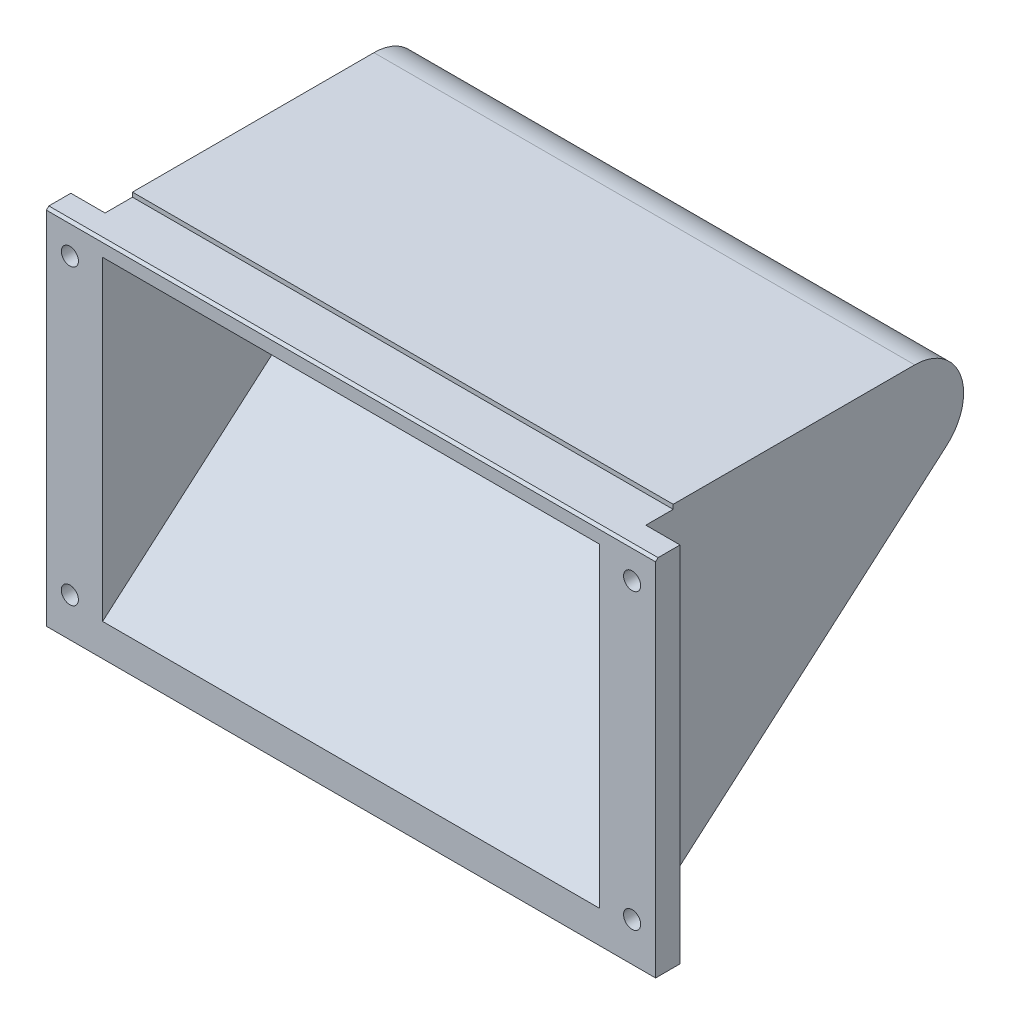
SolidWorks part; units mm, degrees
ref_plane "Front" through (0, 0, 0) normal (0, 0, 1) x (1, 0, 0)
ref_plane "Top" through (0, 0, 0) normal (0, 1, 0) x (1, 0, 0)
ref_plane "Right" through (0, 0, 0) normal (1, 0, 0) x (0, 0, -1)
sketch "Sketch1" plane through (0, 0, 0) normal (1, 0, 0) x (0, 0, -1)
  line L0 (0, 0) -> (60, 0)
  line L1 (63.2707, -8.7819) -> (0, -63.5)
  line L2 (0, 0) -> (0, 5)
  line L3 (0, 0) -> (0, -63.5) construction
  line L4 (0, 5) -> (60, 5)
  line L5 (66.5414, -12.5638) -> (0, -70.1105)
  line L6 (0, -70.1105) -> (0, -63.5)
  arc A0 (60, 0) -> (63.2707, -8.7819) centre (60, -5) cw
  arc A1 (60, 5) -> (66.5414, -12.5638) centre (60, -5) cw
  point P9 (73.4252, 0)
  dimension "D4" = 5
  dimension "D1" = 63.5
  dimension "D2" = 60
  dimension "D3" = 5
extrude "Boss-Extrude1" add sketch "Sketch1" along normal mid plane 101.6
sketch "Sketch3" plane through (50.8, 0, 0) normal (1, 0, 0) x (0, 0, -1)
  line L0 (0, 0) -> (0, -63.5)
  line L6 (0, 5) -> (0, 0)
  line L7 (0, 0) -> (60, 0)
  line L8 (63.2707, -8.7819) -> (0, -63.5)
  line L9 (0, -63.5) -> (0, -70.1105)
  line L10 (0, -70.1105) -> (66.5414, -12.5638)
  line L11 (60, 5) -> (0, 5)
  line L12 (0, 5) -> (0, 0)
  line L13 (0, 0) -> (60, 0)
  line L14 (63.2707, -8.7819) -> (0, -63.5)
  line L15 (0, -63.5) -> (0, -70.1105)
  line L16 (0, -70.1105) -> (66.5414, -12.5638)
  line L17 (60, 5) -> (0, 5)
  arc A2 (63.2707, -8.7819) -> (60, 0) centre (60, -5) ccw
  arc A3 (66.5414, -12.5638) -> (60, 5) centre (60, -5) ccw
  arc A4 (63.2707, -8.7819) -> (60, 0) centre (60, -5) ccw
  arc A5 (66.5414, -12.5638) -> (60, 5) centre (60, -5) ccw
  line M9 (0, 5) -> (0, 0)
  line M10 (0, 0) -> (60, 0)
  arc M11 (60, 0) -> (63.2707, -8.7819) centre (60, -5) cw
  line M12 (63.2707, -8.7819) -> (0, -63.5)
  line M13 (0, -63.5) -> (0, -70.1105)
  line M14 (0, -70.1105) -> (66.5414, -12.5638)
  arc M15 (66.5414, -12.5638) -> (60, 5) centre (60, -5) ccw
  line M16 (60, 5) -> (0, 5)
  dimension "D1" = 0
extrude "Boss-Extrude3" add sketch "Sketch3" along normal blind 4.5 contours M16 M9 M10 M11 M12 M13 M14 M15 | L0 M10 M12 M11 region at (50.8, -21.4686, -23.7908) region at (50.8, 2.5, -1.0267)
mirror "Mirror1" about plane through (0, 0, 0) normal (1, 0, 0) of "Boss-Extrude3"
sketch "Sketch4" plane through (0, 0, 0) normal (0, 0, 1) x (1, 0, 0)
  line L0 (-50.8, 5) -> (-50.8, -63.5)
  line L1 (55.3, 5) -> (-55.3, 5) construction
  line L2 (-50.8, -63.5) -> (50.8, -63.5)
  line L3 (50.8, -63.5) -> (50.8, 5)
  line L4 (50.8, 5) -> (62.3, 5)
  line L5 (62.3, 5) -> (62.3, -70.1105)
  line L6 (62.3, -70.1105) -> (-62.3, -70.1105)
  line L7 (-62.3, -70.1105) -> (-62.3, 5)
  line L8 (-62.3, 5) -> (-50.8, 5)
  line L9 (0, -63.5) -> (0, -70.1105) construction
  line L10 (55.3, 5) -> (55.3, -70.1105) construction
  line L11 (55.3, -70.1105) -> (-55.3, -70.1105) construction
  line M5 (-50.8, -63.5) -> (-50.8, 0)
  line M7 (50.8, 0) -> (50.8, -63.5)
  line M8 (50.8, -63.5) -> (-50.8, -63.5)
  line M9 (55.3, 5) -> (-55.3, 5)
  line M10 (-55.3, 5) -> (-55.3, -70.1105)
  line M11 (-55.3, -70.1105) -> (55.3, -70.1105)
  line M12 (55.3, -70.1105) -> (55.3, 5)
  dimension "D1" = 7
extrude "Boss-Extrude4" add sketch "Sketch4" against normal blind 5 contours L9 L2 L0 M5 M9 M10 M11 | L9 L8 L7 L6 M11 M10 | L9 L6 L5 L4 M11 M12 | L9 L3 M8 M11 M12 M9 M7 region at (-51.7327, 2.5, 0) region at (-58.8, -32.5552, 0) region at (53.05, 4.0673, 0) region at (58.8, -32.5552, 0)
sketch "Sketch6" plane through (0, 0, 0) normal (0, 0, 1) x (1, 0, 0)
  line L0 (62.3, 5) -> (-62.3, 5) construction
  line L1 (-57.5, -2.146) -> (57.5, -2.146) construction
  line L2 (-57.5, -2.146) -> (-57.5, -62.146) construction
  line L3 (-57.5, -62.146) -> (57.5, -62.146) construction
  line L4 (57.5, -2.146) -> (57.5, -62.146) construction
  line L5 (0, 0) -> (0, -2.146) construction
  circle A0 centre (-57.5, -2.146) radius 1.75
  circle A1 centre (-57.5, -62.146) radius 1.75
  circle A2 centre (57.5, -62.146) radius 1.75
  circle A3 centre (57.5, -2.146) radius 1.75
  dimension "D4" = 3.5
  dimension "D1" = 115
  dimension "D2" = 60
  dimension "D3" = 7.146
extrude "Cut-Extrude1" cut sketch "Sketch6" against normal blind 18.75
sketch "Sketch7" plane through (0, 0, 0) normal (0, 0, 1) x (1, 0, 0)
  line L1 (-50.8, 0) -> (50.8, 0)
  line L2 (-50.8, 0) -> (-50.8, 0.5)
  line L3 (-50.8, 0.5) -> (50.8, 0.5)
  line L4 (50.8, 0) -> (50.8, 0.5)
  point P4 (50.8, 0)
  dimension "D1" = 0.5
extrude "Cut-Extrude2" cut sketch "Sketch7" against normal blind 5.461
sketch "Sketch8" plane through (0, 0, 0) normal (0, 0, 1) x (1, 0, 0)
  line L0 (62.3, 5) -> (62.3, -70.1105) construction
  line L1 (-62.3, 5) -> (62.3, 5)
  line L2 (-62.3, 5) -> (-62.3, 4.1)
  line L3 (-62.3, 4.1) -> (62.3, 4.1)
  line L4 (62.3, 5) -> (62.3, 4.1)
  dimension "D1" = 0.9
extrude "Cut-Extrude3" cut sketch "Sketch8" against normal blind 10.6
fillet "Fillet1" radius 0.5 2 edges at (0, 0.5, 0) (0, 4.1, 0) profile chamfer
